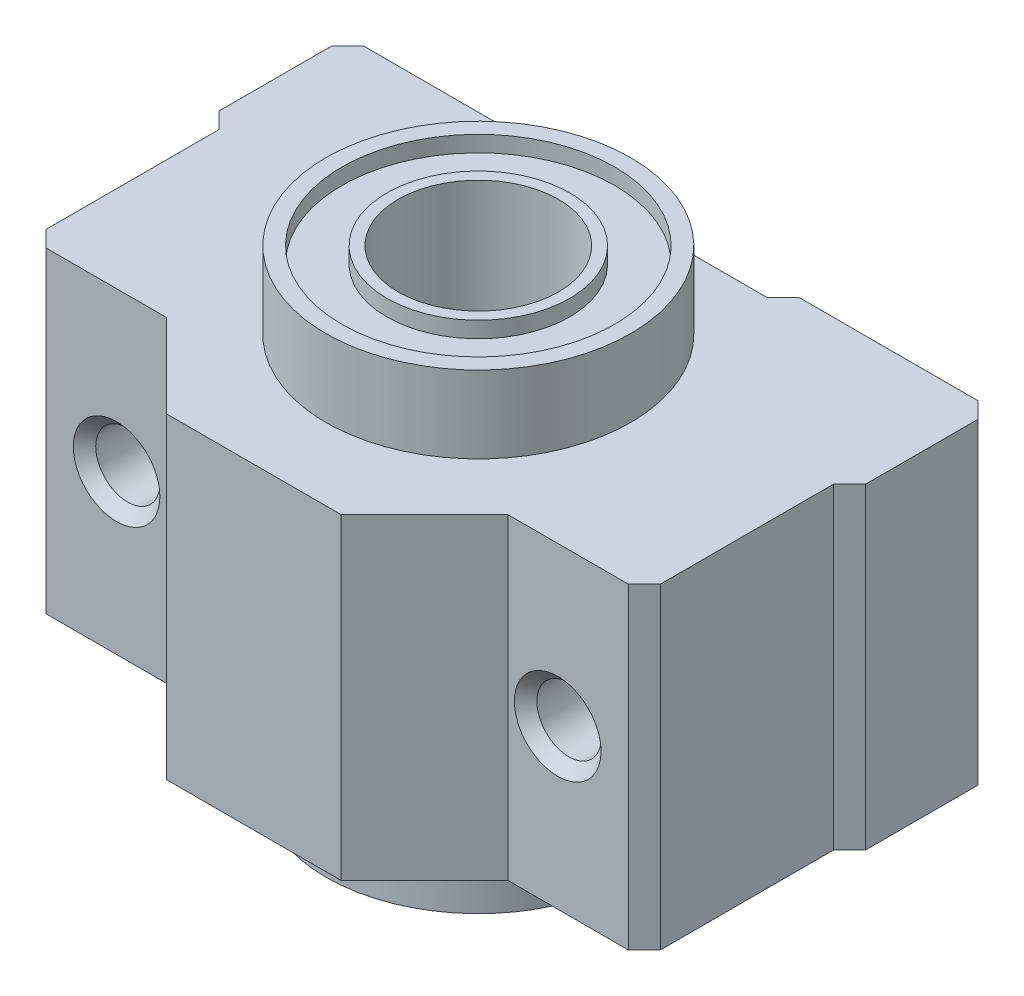
SolidWorks part; units mm, degrees
material "3.0205 (EN-AW 1200)"
ref_plane "Alzado" through (0, 0, 0) normal (0, 0, 1) x (1, 0, 0)
ref_plane "Planta" through (0, 0, 0) normal (0, 1, 0) x (1, 0, 0)
ref_plane "Vista lateral" through (0, 0, 0) normal (1, 0, 0) x (0, 0, -1)
sketch "Croquis1" plane through (0, 0, 0) normal (0, 0, 1) x (1, 0, 0)
  line L1 (-20.15, -9.875) -> (20.15, -9.875)
  line L2 (-20.15, -9.875) -> (-20.15, 9.875)
  line L3 (-20.15, 9.875) -> (20.15, 9.875)
  line L4 (20.15, -9.875) -> (20.15, 9.875)
  line L5 (-20.15, -9.875) -> (20.15, 9.875) construction
  line L6 (-20.15, 9.875) -> (20.15, -9.875) construction
  point P0 (0, 0)
  dimension "D1" = 40.3
  dimension "D2" = 19.75
extrude "Saliente-Extruir1" add sketch "Croquis1" along normal blind 26
sketch "Croquis2" plane through (0, 9.875, 0) normal (0, 1, 0) x (1, 0, 0)
  line L0 (0, 0) -> (0, -26) construction
  line L1 (20.15, 0) -> (-20.15, 0) construction
  line L2 (20.15, -26) -> (-20.15, -26) construction
  line L3 (-7, -1) -> (7, -1)
  line L4 (7, -1) -> (7, 0)
  line L5 (-20.15, -20.8) -> (20.15, -20.8) construction
  line L6 (-20.15, -26) -> (-20.15, 0) construction
  line L7 (20.15, -26) -> (20.15, 0) construction
  line L8 (10.65, 0) -> (10.65, -26) construction
  line L9 (20.15, -9) -> (19.15, -9)
  line L10 (19.15, -9) -> (19.15, -20.8)
  line L11 (19.15, -20.8) -> (10.65, -20.8)
  line L12 (10.65, -20.8) -> (5.45, -26)
  line L13 (5.45, -26) -> (-5.45, -26)
  line L14 (-10.65, -20.8) -> (-5.45, -26)
  line L15 (-19.15, -20.8) -> (-10.65, -20.8)
  line L16 (-19.15, -9) -> (-19.15, -20.8)
  line L17 (-20.15, -9) -> (-19.15, -9)
  line L18 (-7, -1) -> (-7, 0)
  line L19 (20.15, -26) -> (20.15, 0)
  line L20 (20.15, 0) -> (-20.15, 0)
  line L21 (-20.15, -26) -> (-20.15, 0)
  line L22 (-20.15, -26) -> (-5.45, -26)
  line L23 (-20.15, -26) -> (-5.45, -26)
  line L24 (5.45, -26) -> (20.15, -26)
  point P29 (0, -1)
  line M10 (20.15, 0) -> (-20.15, 0)
  line M11 (-20.15, 0) -> (-20.15, -26)
  line M12 (-20.15, -26) -> (20.15, -26)
  line M13 (20.15, -26) -> (20.15, 0)
  dimension "D1" = 7
  dimension "D2" = 1
  dimension "D3" = 20.8
  dimension "D4" = 9.5
  dimension "D5" = 9
  dimension "D6" = 1
  dimension "D7" = 45
extrude "Cortar-Extruir1" cut sketch "Croquis2" against normal blind 20 contours L17 L14 L15 L16 M11 M12 | L11 L12 L9 L10 M12 M13 | L18 L3 L4 M10 region at (0, 9.875, 0.5) region at (-14.8981, 9.875, 22.2145) region at (14.8981, 9.875, 22.2145)
sketch "Croquis3" plane through (0, 0, 0) normal (0, 0, -1) x (-1, 0, 0)
  line L0 (13.75, 0) -> (-13.75, 0) construction
  circle A0 centre (-13.75, 0) radius 2
  circle A1 centre (13.75, 0) radius 2
  point P3 (0, 0)
  dimension "D2" = 4
  dimension "D1" = 27.5
extrude "Cortar-Extruir2" cut sketch "Croquis3" against normal blind 26
sketch "Croquis4" plane through (0, -9.875, 0) normal (0, -1, 0) x (1, 0, 0)
  line L0 (0, 1) -> (0, 26) construction
  line L1 (-7, 1) -> (7, 1) construction
  line L2 (-5.45, 26) -> (5.45, 26) construction
  line L3 (-20.15, 0) -> (-7, 0) construction
  circle A0 centre (0, 12) radius 9.5
  dimension "D1" = 12
  dimension "D2" = 19
extrude "Saliente-Extruir2" add sketch "Croquis4" along normal blind 4.8
mirror "Simetría1" about plane through (0, 0, 0) normal (0, 1, 0) of "Saliente-Extruir2"
sketch "Croquis5" plane through (0, -14.675, 0) normal (0, -1, 0) x (1, 0, 0)
  circle A0 centre (0, 12) radius 5
  dimension "D1" = 10
extrude "Cortar-Extruir3" cut sketch "Croquis5" against normal blind 30
sketch "Croquis6" plane through (0, 14.675, 0) normal (0, 1, 0) x (1, 0, 0)
  circle A0 centre (0, -12) radius 8.5
  circle A1 centre (0, -12) radius 9.5
  circle A2 centre (0, -12) radius 9.5
  circle A5 centre (0, -12) radius 5.7
  circle A6 centre (0, -12) radius 5.7
  dimension "D1" = 0
  dimension "D2" = 1
  dimension "D3" = 0.7
extrude "Cortar-Extruir4" cut sketch "Croquis6" against normal blind 1 contours A0 A6 region at (-8.2596, 14.675, 12)
mirror "Simetría2" about plane through (0, 0, 0) normal (0, 1, 0) of "Cortar-Extruir4"
chamfer "Chaflán1" distance 1 angle 45 8 edges at (-19.15, 0, 20.8) (-20.15, 0, 9) (19.15, 0, 20.8) (20.15, 0, 9) (-20.15, 0, 0) (20.15, 0, 0) (7, 0, 0) (-7, 0, 0)
chamfer "Chaflán2" distance 0.7 angle 45 4 edges at (11.75, 0, 20.8) (11.75, 0, 0) (-15.75, 0, 0) (-11.75, 0, 20.8)
